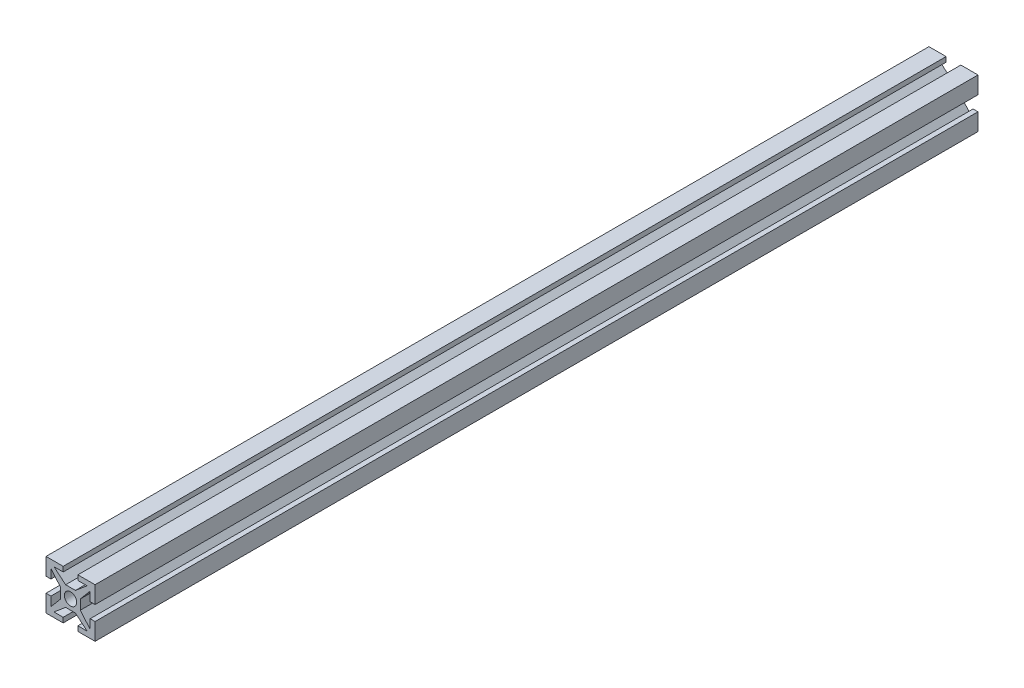
SolidWorks part; units mm, degrees
ref_plane "Front Plane" through (0, 0, 0) normal (0, 0, 1) x (1, 0, 0)
ref_plane "Top Plane" through (0, 0, 0) normal (0, 1, 0) x (1, 0, 0)
ref_plane "Right Plane" through (0, 0, 0) normal (1, 0, 0) x (0, 0, -1)
sketch "Esquisse2" plane through (0, 0, 0) normal (0, 0, 1) x (1, 0, 0)
  line L0 (-1, -2) -> (1, -2)
  line L1 (1, -2) -> (3.3835, -4)
  line L2 (3.3835, -4) -> (1.5, -4)
  line L3 (1.5, -4) -> (1.5, -5)
  line L4 (1.5, -5) -> (5, -5)
  line L5 (-1, -2) -> (-3.3835, -4)
  line L6 (-3.3835, -4) -> (-1.5, -4)
  line L7 (-1.5, -4) -> (-1.5, -5)
  line L8 (-1.5, -5) -> (-5, -5)
  line L9 (-5, -5) -> (-5, -1.5)
  line L10 (-5, -1.5) -> (-4, -1.5)
  line L11 (-4, -1.5) -> (-4, -3.3835)
  line L12 (-4, -3.3835) -> (-2, -1)
  line L13 (-2, -1) -> (-2, 1)
  line L14 (-2, 1) -> (-4, 3.3835)
  line L15 (-4, 3.3835) -> (-4, 1.5)
  line L16 (-4, 1.5) -> (-5, 1.5)
  line L17 (-5, 1.5) -> (-5, 5)
  line L18 (-5, 5) -> (-1.5, 5)
  line L19 (-1.5, 5) -> (-1.5, 4)
  line L20 (-1.5, 4) -> (-3.3835, 4)
  line L21 (-3.3835, 4) -> (-1, 2)
  line L22 (-1, 2) -> (1, 2)
  line L23 (1, 2) -> (3.3835, 4)
  line L24 (3.3835, 4) -> (1.5, 4)
  line L25 (1.5, 4) -> (1.5, 5)
  line L26 (1.5, 5) -> (5, 5)
  line L27 (5, 5) -> (5, 1.5)
  line L28 (5, 1.5) -> (4, 1.5)
  line L29 (4, 1.5) -> (4, 3.3835)
  line L30 (4, 3.3835) -> (2, 1)
  line L31 (2, -1) -> (2, 1)
  line L32 (2, -1) -> (4, -3.3835)
  line L33 (4, -3.3835) -> (4, -1.5)
  line L34 (4, -1.5) -> (5, -1.5)
  line L35 (5, -1.5) -> (5, -5)
  circle A0 centre (0, 0) radius 1.25
  point P4 (0, -2)
  point P34 (0, 2)
  point P40 (2, 0)
  dimension "D4" = 2.5
  dimension "D1" = 2
  dimension "D2" = 3.5
  dimension "D3" = 1
  dimension "D5" = 10
  dimension "D6" = 10
  dimension "D7" = 140
  dimension "D8" = 4
  dimension "D9" = 4
  dimension "D10" = 3.5
  dimension "D11" = 3
extrude "Main Extrusion" add sketch "Esquisse2" along normal blind 180
